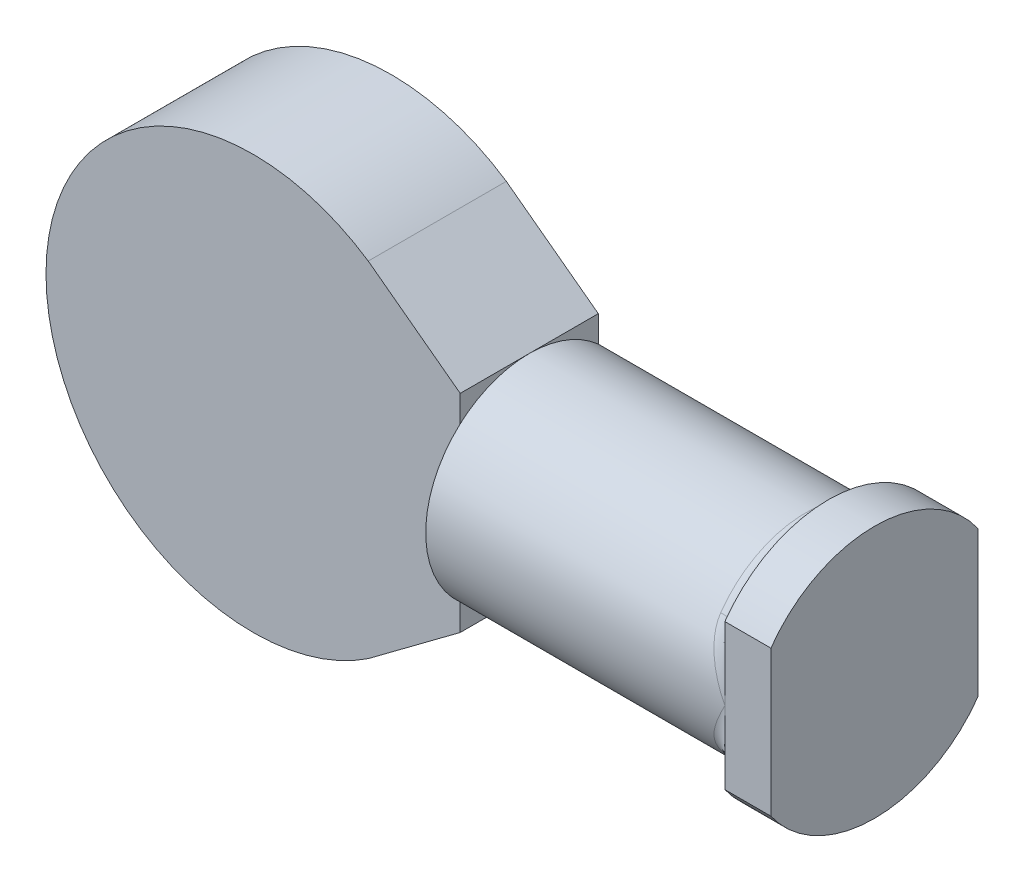
SolidWorks part; units mm, degrees
ref_plane "Alzado" through (0, 0, 0) normal (0, 0, 1) x (1, 0, 0)
ref_plane "Planta" through (0, 0, 0) normal (0, 1, 0) x (1, 0, 0)
ref_plane "Vista lateral" through (0, 0, 0) normal (1, 0, 0) x (0, 0, -1)
sketch "Croquis1" plane through (0, 0, 0) normal (0, 0, 1) x (1, 0, 0)
  line L0 (0, 0) -> (15.3661, 0) construction
  line L1 (9, -4.5) -> (9, 4.5)
  line L2 (9, 4.5) -> (5.0033, 7.4811)
  line L3 (9, -4.5) -> (5.0033, -7.4811)
  arc A0 (5.0033, 7.4811) -> (5.0033, -7.4811) centre (0, 0) ccw
  point P7 (9, 0)
  dimension "D1" = 18
  dimension "D2" = 4.5
extrude "Saliente-Extruir1" add sketch "Croquis1" along normal mid plane 6
sketch "Croquis2" plane through (9, 0, 0) normal (1, 0, 0) x (0, 0, -1)
  circle A0 centre (0, 0) radius 4.5
  dimension "D1" = 9
extrude "Saliente-Extruir2" add sketch "Croquis2" along normal blind 13
sketch "Croquis3" plane through (22, 0, 0) normal (1, 0, 0) x (0, 0, -1)
  line L0 (0, 0) -> (-4.5, 0) construction
  line L1 (-4.5, -3.1623) -> (-4.5, 3.1623)
  line L2 (0, 0) -> (0, 5.5) construction
  line L3 (4.5, -3.1623) -> (4.5, 3.1623)
  arc A0 (-4.5, -3.1623) -> (4.5, -3.1623) centre (0, 0) ccw
  circle A1 centre (0, 0) radius 4.5 construction
  arc A2 (4.5, 3.1623) -> (-4.5, 3.1623) centre (0, 0) ccw
  dimension "D1" = 11
extrude "Saliente-Extruir3" add sketch "Croquis3" along normal blind 2
fillet "Redondeo1" radius 1 2 edges at (22, -4.5, 0) (22, 4.5, 0)
